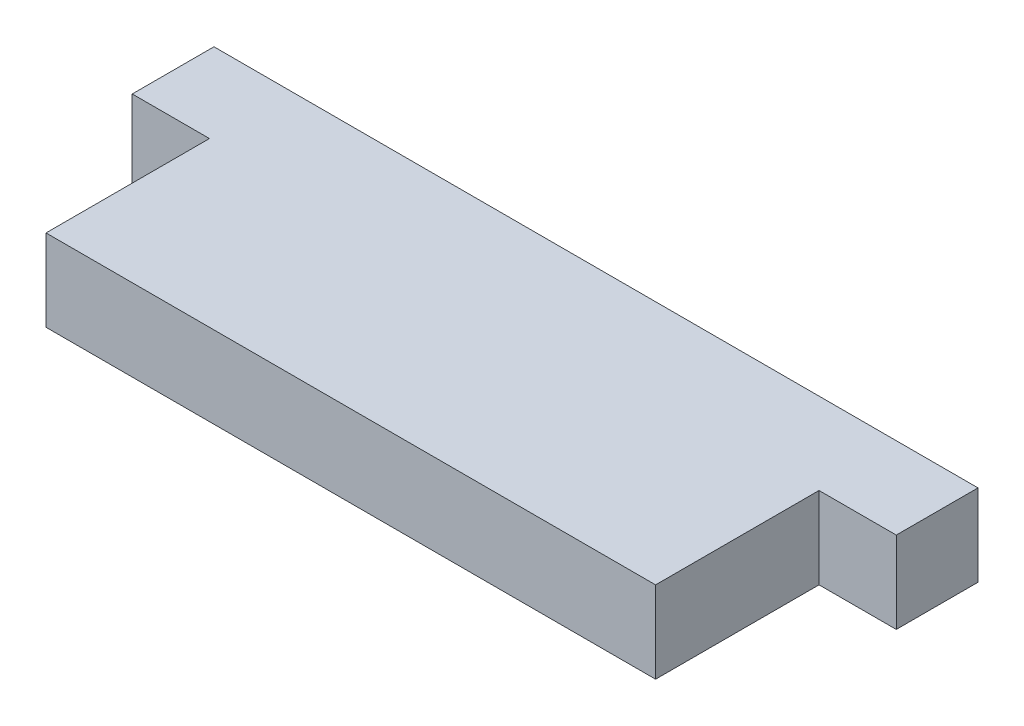
SolidWorks part; units mm, degrees
ref_plane "Front Plane" through (0, 0, 0) normal (0, 0, 1) x (1, 0, 0)
ref_plane "Top Plane" through (0, 0, 0) normal (0, 1, 0) x (1, 0, 0)
ref_plane "Right Plane" through (0, 0, 0) normal (1, 0, 0) x (0, 0, -1)
sketch "Sketch1" plane through (0, 0, 0) normal (0, 1, 0) x (1, 0, 0)
  line L0 (0, 0) -> (0, 12.7)
  line L1 (0, 0) -> (47.3601, 0)
  line L3 (47.3601, 0) -> (47.3601, 12.7)
  line L4 (-6.0001, 19.05) -> (53.3602, 19.05)
  line L5 (-6.0001, 19.05) -> (-6.0001, 12.7)
  line L6 (53.3602, 19.05) -> (53.3602, 12.7)
  line L7 (-6.0001, 12.7) -> (0, 12.7)
  line L8 (47.3601, 12.7) -> (53.3602, 12.7)
  dimension "D1" = 12.7
  dimension "D2" = 47.3601
  dimension "D3" = 6.35
  dimension "D4" = 6.0001
  dimension "D5" = 6.0001
extrude "Boss-Extrude1" add sketch "Sketch1" along normal blind 6.35
equation "\"vigorwidth\"= 0.472441in"
equation "\"vigorflangewidth\"= 0.731102in"
equation "\"vigorflangelength\"= 0.131102in"
equation "\"vigorscrewsize\"= 0.066535in"
equation "\"vigorholeoffsetwid\"= 0.0646653in"
equation "\"vigorholeoffsetlen\"= 0.065551in"
equation "\"vigorflangedepth\"= 0.0901575in"
equation "\"vigordiscdepth\"= 0.0492126in"
equation "\"vigormotordepth\"= 1.12362in"
equation "\"vigortipdepth\"= 0.259055in"
equation "\"vigoraxlewidth\"= 0.173622in"
equation "\"vigorcutlen\"= 0.0480315in"
equation "\"vigoraxledepth\"= 0.159055in"
equation "\"rackoffset\"=.236224in"
equation "\"Slot\"=.25in"
equation "\"MotorMountLegLength\"=.25in"
equation "\"GearOffset\"=.264907in"
equation "\"D4@Sketch1\"=\"rackoffset\""
equation "\"D5@Sketch1\"=\"rackoffset\""
equation "\"MotorMountWidth\"=1.86457"
equation "\"D2@Sketch1\"=\"MotorMountWidth\""
